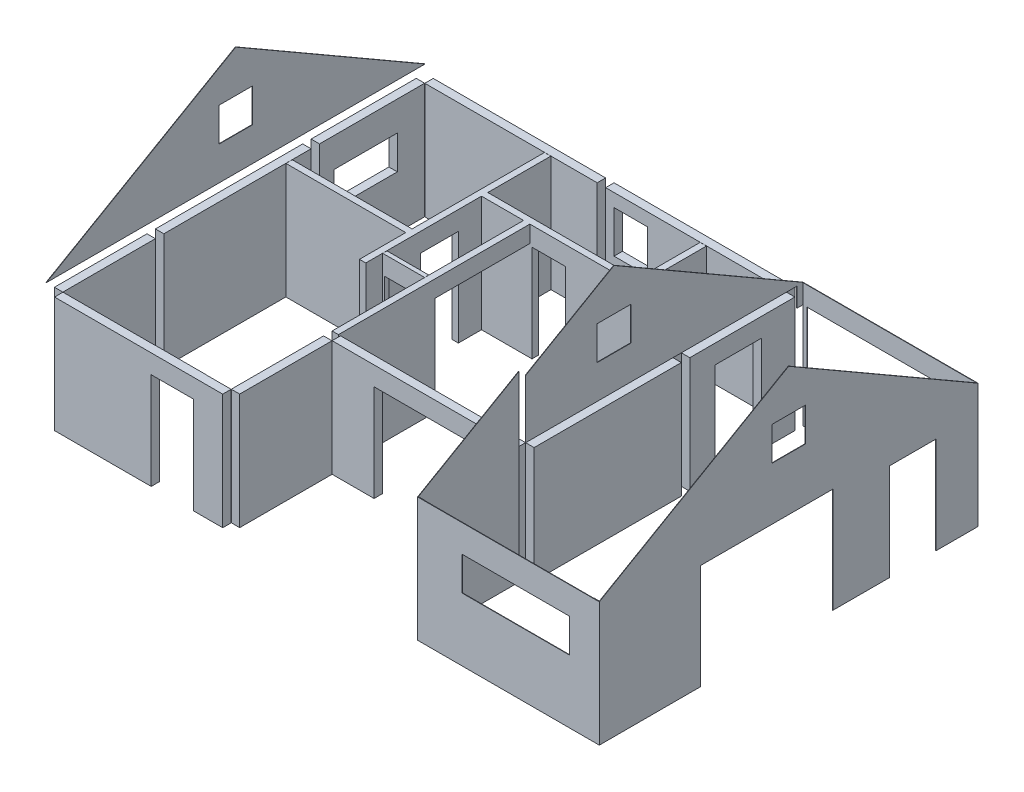
SolidWorks part; units mm, degrees
ref_plane "Спереди" through (0, 0, 0) normal (0, 0, 1) x (1, 0, 0)
ref_plane "Сверху" through (0, 0, 0) normal (0, 1, 0) x (1, 0, 0)
ref_plane "Справа" through (0, 0, 0) normal (1, 0, 0) x (0, 0, -1)
sketch "Эскиз1" plane through (0, 0, 0) normal (0, 1, 0) x (1, 0, 0)
  line L0 (9000, -6600) -> (4400, -6600) construction
  line L1 (0, 0) -> (9000, 0) construction
  line L2 (0, 0) -> (0, -8800) construction
  line L3 (0, -9000) -> (4400, -9000) construction
  line L4 (9000, 0) -> (9000, -6600) construction
  line L5 (4400, -6600) -> (4400, -9000) construction
  line L6 (8800, -203) -> (9000, -203)
  line L7 (203, 0) -> (4300, 0)
  line L8 (203, 0) -> (203, -200)
  line L9 (203, -200) -> (4300, -200)
  line L12 (0, -200) -> (0, -2700)
  line L14 (200, -200) -> (200, -2700)
  line L15 (203, -9000) -> (2500, -9000)
  line L16 (203, -9000) -> (203, -8800)
  line L17 (203, -8800) -> (2500, -8800)
  line L19 (4400, -8797) -> (4200, -8797)
  line L20 (4400, -8797) -> (4400, -6603)
  line L22 (4200, -8797) -> (4200, -6603)
  line L24 (9000, -203) -> (9000, -1000)
  line L26 (8800, -203) -> (8800, -1000)
  line L27 (8797, -6600) -> (7597, -6600)
  line L28 (8797, -6600) -> (8797, -6400)
  line L29 (8797, -6400) -> (7597, -6400)
  line L31 (2500, -8800) -> (2500, -9000)
  line L32 (3500, -8800) -> (3500, -9000)
  line L33 (3500, -8800) -> (4200, -8800)
  line L34 (3500, -9000) -> (4200, -9000)
  line L35 (5597, -6400) -> (5597, -6600)
  line L36 (7597, -6400) -> (7597, -6600)
  line L37 (5597, -6400) -> (4400, -6400)
  line L38 (5597, -6600) -> (4400, -6600)
  line L39 (8800, -1000) -> (9000, -1000)
  line L41 (8800, -2100) -> (9000, -2100)
  line L42 (8800, -2100) -> (8800, -2700)
  line L43 (9000, -2100) -> (9000, -2700)
  line L47 (4200, -6400) -> (4350, -6400)
  line L83 (4200, -6603) -> (4400, -6603)
  line L92 (4200, -4100) -> (4350, -4100)
  line L93 (4200, -4100) -> (4200, -6400)
  line L94 (4350, -4100) -> (4350, -6400)
  line L100 (200, -8800) -> (0, -8800)
  line L101 (4200, -8800) -> (4200, -9000)
  line L102 (4400, -6400) -> (4400, -6600)
  line L103 (8800, -6400) -> (9000, -6400)
  line L104 (0, -200) -> (200, -200)
  line L108 (0, -4500) -> (0, -6400)
  line L109 (200, -4500) -> (200, -6400)
  line L110 (8800, 0) -> (8800, -200)
  line L111 (4300, 0) -> (4300, -200)
  line L113 (4500, 0) -> (4500, -200)
  line L114 (4500, 0) -> (8800, 0)
  line L115 (4500, -200) -> (8800, -200)
  line L116 (0, -9000) -> (0, -8800) construction
  line L117 (-6170.9643, 0) -> (12200, 0) construction
  line L118 (0, 1882.3698) -> (0, -11726.3327) construction
  line L119 (-6170.9643, -4500) -> (10764.3505, -4500) construction
  line L120 (1000, -4500) -> (2250, -4500) construction
  line L121 (-6170.9643, -9000) -> (12200, -9000) construction
  line L122 (1000, -4500) -> (1000, -4600) construction
  line L123 (1000, -4600) -> (2250, -4600) construction
  line L124 (2250, -4500) -> (2250, -4600) construction
  line L125 (1000, -4500) -> (2250, -4600) construction
  line L126 (1000, -4600) -> (2250, -4500) construction
  line L131 (0, -2700) -> (200, -2700)
  line L132 (0, -2900) -> (0, -4500)
  line L137 (3050, -203) -> (3200, -203)
  line L138 (3050, -203) -> (3050, -2400)
  line L139 (3050, -2400) -> (3200, -2400)
  line L140 (3200, -203) -> (3200, -1700)
  line L141 (3050, -203) -> (3200, -2400) construction
  line L142 (3050, -2400) -> (3200, -203) construction
  line L143 (3050, -3300) -> (3200, -3300)
  line L144 (3050, -3300) -> (3050, -3350)
  line L145 (3050, -4600) -> (3200, -4600)
  line L146 (3200, -3300) -> (3200, -4600)
  line L147 (3050, -3300) -> (3200, -4600) construction
  line L148 (3050, -4600) -> (3200, -3300) construction
  line L149 (4150, -4100) -> (4197, -4100)
  line L150 (4150, -4100) -> (4150, -4200)
  line L151 (4150, -4200) -> (4197, -4200)
  line L152 (4197, -4100) -> (4197, -4200)
  line L153 (4150, -4100) -> (4197, -4200) construction
  line L154 (4150, -4200) -> (4197, -4100) construction
  line L155 (203, -3350) -> (3050, -3350)
  line L156 (203, -3350) -> (203, -3500)
  line L157 (203, -3500) -> (3050, -3500)
  line L159 (203, -3350) -> (3050, -3500) construction
  line L160 (203, -3500) -> (3050, -3350) construction
  line L161 (6400, -3500) -> (8800, -3500) construction
  line L162 (4400, 2182.3698) -> (4400, -11426.3327) construction
  line L163 (5200, -1700) -> (6750, -1700)
  line L164 (9000, 2182.3698) -> (9000, -11265.4622) construction
  line L165 (5200, -1700) -> (5200, -1850)
  line L166 (5200, -1850) -> (6900, -1850)
  line L167 (6900, -1700) -> (6900, -1850)
  line L168 (5200, -1700) -> (6900, -1850) construction
  line L169 (5200, -1850) -> (6900, -1700) construction
  line L170 (5800, -2800) -> (8797, -2800) construction
  line L171 (5800, -2800) -> (5800, -2900) construction
  line L172 (5800, -2900) -> (8797, -2900) construction
  line L173 (8797, -2800) -> (8797, -2900) construction
  line L174 (5800, -2800) -> (8797, -2900) construction
  line L175 (5800, -2900) -> (8797, -2800) construction
  line L176 (6750, -203) -> (6900, -203)
  line L177 (6750, -203) -> (6750, -1700)
  line L179 (6900, -203) -> (6900, -1700)
  line L180 (6750, -203) -> (6900, -1700) construction
  line L181 (6750, -1700) -> (6900, -203) construction
  line L186 (3200, -1700) -> (4400, -1700)
  line L188 (3200, -1850) -> (4400, -1850)
  line L189 (4400, -1700) -> (4400, -1850)
  line L190 (3200, -1700) -> (4400, -1850) construction
  line L191 (3200, -1850) -> (4400, -1700) construction
  line L192 (5800, -2900) -> (6400, -2900) construction
  line L193 (5800, -2900) -> (5800, -3500) construction
  line L194 (5800, -3500) -> (6400, -3500) construction
  line L195 (6400, -2900) -> (6400, -3500) construction
  line L196 (5800, -2900) -> (6400, -3500) construction
  line L197 (5800, -3500) -> (6400, -2900) construction
  line L198 (12200, 0) -> (12200, -9000) construction
  line L199 (5350, -4400) -> (5800, -3500) construction
  line L204 (3203, -4100) -> (3250, -4100)
  line L205 (3203, -4100) -> (3203, -4200)
  line L206 (3203, -4200) -> (3250, -4200)
  line L207 (3250, -4100) -> (3250, -4200)
  line L208 (3203, -4100) -> (3250, -4200) construction
  line L209 (3203, -4200) -> (3250, -4100) construction
  line L210 (4350, -4400) -> (5350, -4400) construction
  line L211 (4350, -4400) -> (4350, -6400) construction
  line L212 (4350, -6400) -> (5350, -6400) construction
  line L213 (5350, -4400) -> (5350, -6400) construction
  line L214 (4350, -4400) -> (5350, -6400) construction
  line L215 (4350, -6400) -> (5350, -4400) construction
  line L216 (3200, -1850) -> (3200, -2400)
  line L217 (0, -2900) -> (200, -2900)
  line L218 (200, -2900) -> (200, -4500)
  line L219 (0, -6400) -> (200, -6400)
  line L220 (0, -6600) -> (0, -8800)
  line L221 (0, -6600) -> (200, -6600)
  line L222 (200, -6600) -> (200, -8800)
  line L223 (3050, -3500) -> (3050, -4600)
  line L224 (8800, -2700) -> (9000, -2700)
  line L225 (8800, -2900) -> (8800, -6400)
  line L226 (8800, -2900) -> (9000, -2900)
  line L227 (9000, -2900) -> (9000, -6400)
  point P14 (3226.5, -4150)
  point P17 (7298.5, -2850)
  point P41 (1625, -4550)
  point P52 (3125, -1301.5)
  point P62 (3125, -3950)
  point P67 (4173.5, -4150)
  point P72 (1626.5, -3425)
  point P103 (3800, -1775)
  point P104 (6825, -951.5)
  point P105 (4150, -4150)
  point P108 (6050, -1775)
  point P120 (6750, -951.5)
  point P122 (6100, -3200)
  point P127 (4850, -5400)
  dimension "D2" = 6600
  dimension "D3" = 9000
  dimension "D4" = 200
  dimension "D5" = 3
  dimension "D6" = 3
  dimension "D7" = 3
  dimension "D8" = 9000
  dimension "D9" = 200
  dimension "D10" = 3
  dimension "D11" = 3
  dimension "D12" = 700
  dimension "D13" = 50
  dimension "D14" = 4500
  dimension "D15" = 4000
  dimension "D16" = 100
  dimension "D17" = 800
  dimension "D18" = 4400
  dimension "D19" = 4600
  dimension "D20" = 1000
  dimension "D21" = 800
  dimension "D22" = 2000
  dimension "D23" = 1200
  dimension "D24" = 1100
  dimension "D25" = 3
  dimension "D26" = 200
  dimension "D27" = 1000
  dimension "D29" = 200
  dimension "D30" = 4500
  dimension "D31" = 3
  dimension "D32" = 200
  dimension "D33" = 3
  dimension "D34" = 900
  dimension "D35" = 3
  dimension "D36" = 900
  dimension "D37" = 50
  dimension "D38" = 150
  dimension "D39" = 100
  dimension "D40" = 3
  dimension "D41" = 2850
  dimension "D42" = 3150
  dimension "D43" = 1250
  dimension "D44" = 200
  dimension "D46" = 3550
  dimension "D47" = 1500
  dimension "D48" = 800
  dimension "D49" = 1900
  dimension "D50" = 950
  dimension "D51" = 3
  dimension "D53" = 800
  dimension "D54" = 3
  dimension "D55" = 4450
  dimension "D56" = 3500
  dimension "D57" = 2400
  dimension "D58" = 3000
  dimension "D59" = 1400
  dimension "D60" = 2650
  dimension "D61" = 600
  dimension "D63" = 2900
  dimension "D64" = 2300
  dimension "D65" = 1247
  dimension "D66" = 3200
  dimension "D67" = 2000
  dimension "D68" = 1000
  dimension "D72" = 200
extrude "Бобышка-Вытянуть3" add sketch "Эскиз1" along normal blind 2750 contours L155 | L42 L103 L43 L41 | L26 L39 L24 L6 | L113 L115 L110 L114 | L216 L188 L189 L186 L140 L137 L138 L139 | L179 L176 L177 L163 L165 L166 L167 | L157 L223 L145 L146 L143 L144 L155 L156 | L108 L219 L109 L218 L217 L132 | L222 L221 L220 L100 | L144 L145 L146 L143 | L140 L139 L138 L137 | L27 L36 L29 L28 | L8 L9 L111 L7 | L14 L131 L12 L104 | L100 L108 L132 L217 L218 L109 | L47 L94 L92 L93 | L35 L38 L102 L37 | L171 L172 L173 L170 | L19 L22 L83 L20 | L32 L34 L101 L33 | L15 L31 L17 L16 | L122 L120 L124 L123 | L205 L204 L207 L206 | L150 L149 L152 L151 | L165 L163 L167 L166 | L103 L227 L226 L225 region at (8900, 0, 601.5) region at (8900, 0, 2400) region at (100, 0, 7700) region at (100, 0, 4650) region at (6650, 0, 100) region at (3125, 0, 228.7863) region at (3125, 0, 3332.668) region at (5975, 0, 1723.6698)
sketch "Эскиз2" plane through (0, 0, 0) normal (-1, 0, 0) x (0, 0, 1)
  line L2 (850, 1250) -> (2350, 1250)
  line L3 (850, 1250) -> (850, 2050)
  line L4 (850, 2050) -> (2350, 2050)
  line L5 (2350, 1250) -> (2350, 2050)
  line L7 (200, 0) -> (2700, 0) construction
  line L8 (3350, 2750) -> (3350, 0) construction
  dimension "D1" = 1500
  dimension "D2" = 800
  dimension "D3" = 1250
  dimension "D4" = 1000
extrude "Вырез-Вытянуть2" cut sketch "Эскиз2" against normal blind 250
sketch "Эскиз3" plane through (0, 0, 0) normal (0, 0, -1) x (-1, 0, 0)
  line L0 (-4500, 0) -> (-8800, 0) construction
  line L8 (-5500, 2440) -> (-4700, 2440)
  line L9 (-5500, 2440) -> (-5500, 1440)
  line L10 (-5500, 1440) -> (-4700, 1440)
  line L11 (-4700, 2440) -> (-4700, 1440)
  line L15 (-4500, 2750) -> (-4500, 0) construction
  dimension "D1" = 200
  dimension "D2" = 2440
  dimension "D3" = 800
  dimension "D4" = 1000
  dimension "D5" = 1440
extrude "Вырез-Вытянуть3" cut sketch "Эскиз3" against normal blind 593
sketch "Эскиз4" plane through (0, 2750, 0) normal (0, 1, 0) x (1, 0, 0)
  line L6 (3203, -4100) -> (3250, -4100) construction
  line L7 (3226.5, -4100) -> (4173.5, -4100)
  line L8 (3226.5, -4100) -> (3226.5, -4200)
  line L9 (3226.5, -4200) -> (4173.5, -4200)
  line L10 (4173.5, -4100) -> (4173.5, -4200)
  line L11 (4150, -4200) -> (4197, -4200) construction
  line L13 (3050, -2346.4504) -> (3200, -2346.4504)
  line L14 (3050, -2346.4504) -> (3050, -3325)
  line L15 (3050, -3325) -> (3200, -3325)
  line L16 (3200, -2346.4504) -> (3200, -3325)
  line L19 (4249.5007, -1700) -> (5402.0861, -1700)
  line L20 (4249.5007, -1700) -> (4249.5007, -1850)
  line L21 (4249.5007, -1850) -> (5402.0861, -1850)
  line L22 (5402.0861, -1700) -> (5402.0861, -1850)
  line L24 (5200, -1850) -> (6900, -1850) construction
  line L29 (3050, -203) -> (3050, -2400) construction
  line L30 (5597, -6400) -> (4400, -6400) construction
  line L31 (5423.0031, -6400) -> (7690.4362, -6400)
  line L32 (5423.0031, -6400) -> (5423.0031, -6600)
  line L33 (5423.0031, -6600) -> (7690.4362, -6600)
  line L34 (7690.4362, -6400) -> (7690.4362, -6600)
  line L35 (8797, -6600) -> (7597, -6600) construction
  line L36 (8800, -203) -> (8800, -1000) construction
  line L37 (8800, -900.8258) -> (9000, -900.8258)
  line L38 (8800, -900.8258) -> (8800, -2153.976)
  line L39 (8800, -2153.976) -> (9000, -2153.976)
  line L40 (9000, -900.8258) -> (9000, -2153.976)
  line L41 (9000, -2100) -> (9000, -2700) construction
  line L42 (3500, -9000) -> (4200, -9000) construction
  line L43 (2379.0159, -8797) -> (3597.5552, -8797)
  line L44 (2379.0159, -8797) -> (2379.0159, -9000)
  line L45 (2379.0159, -9000) -> (3597.5552, -9000)
  line L46 (3597.5552, -8797) -> (3597.5552, -9000)
  line L47 (3200, -1850) -> (3200, -2400) construction
  line L48 (3200, -1700) -> (4400, -1700) construction
extrude "Бобышка-Вытянуть4" add sketch "Эскиз4" against normal offset from surface (450 mm away) 2300 up to face at (8900, 0, 601.5)
ref_plane "Плоскость1" through (13000, 0, 0) normal (1, 0, 0) x (0, 0, -1)
sketch "Эскиз5" plane through (13000, 0, 0) normal (1, 0, 0) x (0, 0, -1)
  line L0 (-4500, 5721.2813) -> (-4500, -150) construction
  line L1 (-6600, -150) -> (0, -150) construction
  line L2 (-4500, 5548.0762) -> (-9000, 2950)
  line L3 (-9000, 2950) -> (-9000, 0)
  line L5 (0, 2950) -> (0, 0)
  line L6 (-4500, 5548.0762) -> (0, 2950)
  line L7 (-8800, 0) -> (-9000, 0) construction
  line L8 (-9000, 0) -> (-8750, 0) construction
  line L9 (-9000, 0) -> (0, 0)
extrude "Бобышка-Вытянуть5" add sketch "Эскиз5" along normal blind 150 separate body
sketch "Эскиз6" plane through (13000, 0, 0) normal (1, 0, 0) x (0, 0, -1)
  line L0 (-9000, 0) -> (0, 0) construction
  line L1 (-1000, 2300) -> (-2100, 2300)
  line L2 (-1000, 2300) -> (-1000, 0)
  line L3 (-1000, 0) -> (-2100, 0)
  line L4 (-2100, 2300) -> (-2100, 0)
  line L5 (0, 2494.3376) -> (50, 2494.3376) construction
  line L6 (-6600, -150) -> (-3450, -150)
  line L7 (-6600, -150) -> (-6600, 2494.3376)
  line L8 (-6600, 2494.3376) -> (-3450, 2494.3376)
  line L9 (-3450, -150) -> (-3450, 2494.3376)
  line L10 (-3450, 50) -> (-3450, 2950) construction
  point P11 (-3450, 2494.3376)
  dimension "D1" = 3150
  dimension "D2" = 1100
extrude "Вырез-Вытянуть5" cut sketch "Эскиз6" along normal blind 670
sketch "Эскиз8" plane through (0, 0, 0) normal (-1, 0, 0) x (0, 0, 1)
  line L0 (4500, 5548.0762) -> (0, 2950)
  line L1 (0, 2950) -> (9000, 2950)
  line L2 (9000, 2950) -> (4500, 5548.0762)
  line L3 (4500, 5548.0762) -> (4500, 2950) construction
  line L4 (2350, 1250) -> (2350, 2050) construction
  line L5 (4100, 4550) -> (4900, 4550)
  line L6 (4100, 4550) -> (4100, 3750)
  line L7 (4100, 3750) -> (4900, 3750)
  line L8 (4900, 4550) -> (4900, 3750)
  dimension "D1" = 800
extrude "Бобышка-Вытянуть8" add sketch "Эскиз8" against normal blind 10 separate body
sketch "Эскиз9" plane through (9000, 0, 0) normal (1, 0, 0) x (0, 0, -1)
  line L0 (-6600, 0) -> (-6600, 2950)
  line L1 (-6600, 2750) -> (-6600, 0) construction
  line L2 (-6600, 2950) -> (0, 2950)
  line L3 (0, 2950) -> (-4500, 5548.0762)
  line L4 (-4500, 5548.0762) -> (-9000, 2950)
  line L5 (-9000, 2950) -> (-9000, 0)
  line L6 (-9000, 0) -> (-6600, 0)
extrude "Бобышка-Вытянуть9" add sketch "Эскиз9" against normal blind 170 separate body
sketch "Эскиз10" plane through (0, 0, 0) normal (0, -1, 0) x (1, 0, 0)
  line L0 (13000, 9000) -> (13000, 6600) construction
  line L1 (9000, 9000) -> (13000, 9000)
  line L2 (9000, 9000) -> (9000, 8850)
  line L3 (9000, 8850) -> (13000, 8850)
  line L4 (13000, 9000) -> (13000, 8850)
  line L5 (13150, 9000) -> (13000, 9000) construction
  line L6 (9000, 6600) -> (9000, 0) construction
  line L7 (13000, 0) -> (12250, 0)
  line L8 (13000, 0) -> (13000, 150)
  line L9 (13000, 150) -> (12250, 150)
  line L10 (12250, 0) -> (12250, 150)
  line L11 (9000, 150) -> (9100, 150)
  line L12 (9000, 150) -> (9000, 0)
  line L13 (9000, 0) -> (9100, 0)
  line L14 (9100, 150) -> (9100, 0)
  line L15 (12250, 160) -> (12250, 10) construction
  point P21 (0, 0)
  point P23 (0, 0)
  point P24 (0, 0)
  point P25 (0, 0)
  point P26 (12250, 150)
extrude "Бобышка-Вытянуть10" add sketch "Эскиз10" against normal up to vertex (2950 mm away) up to point (9000, 2950, 9000)
sketch "Эскиз11" plane through (0, 0, 6400) normal (0, 0, -1) x (-1, 0, 0)
  line L0 (-203, 0) -> (-4300, 0) construction
  line L1 (-7597, 2300) -> (-5397, 2300)
  line L2 (-7597, 2300) -> (-7597, -335.5255)
  line L3 (-7597, -335.5255) -> (-5397, -335.5255)
  line L4 (-5397, 2300) -> (-5397, -335.5255)
  line L5 (-12440, 2950) -> (-12440, 50) construction
  line L6 (-2500, 2300) -> (-3500, 2300)
  line L7 (-2500, 2300) -> (-2500, -123.1481)
  line L8 (-2500, -123.1481) -> (-3500, -123.1481)
  line L9 (-3500, 2300) -> (-3500, -123.1481)
  line L11 (-9890, 2300) -> (-12440, 2300)
  line L12 (-9890, 2300) -> (-9890, 1500)
  line L13 (-9890, 1500) -> (-12440, 1500)
  line L14 (-12440, 2300) -> (-12440, 1500)
  line L15 (-9000, 0) -> (-13000, 0) construction
  line L17 (-9890, 2950) -> (-9890, 50) construction
  dimension "D1" = 1500
  dimension "D2" = 800
  dimension "D3" = 2200
  dimension "D4" = 2300
  dimension "D5" = 2550
extrude "Вырез-Вытянуть6" cut sketch "Эскиз11" against normal blind 5123
sketch "Эскиз12" plane through (0, 0, 0) normal (-1, 0, 0) x (0, 0, 1)
  line L0 (2424.8711, 2950) -> (2424.8711, 4350) construction
  line L1 (0, 2950) -> (9000, 2950) construction
  line L2 (4500, 5548.0762) -> (0, 2950) construction
  line L3 (2424.8711, 4350) -> (3290.8965, 4850) construction
  line L4 (3290.8965, 4850) -> (5709.1035, 4850) construction
  line L5 (9000, 2950) -> (4500, 5548.0762) construction
  line L6 (5709.1035, 4850) -> (6575.1289, 4350) construction
  line L7 (6575.1289, 4350) -> (6575.1289, 2950) construction
  line L8 (4500, 5548.0762) -> (4500, 4850) construction
  dimension "D1" = 1900
  dimension "D2" = 2418.2069
  dimension "D3" = 1400
  dimension "D4" = 4150.2577
extrude "Вырез-Вытянуть7" cut sketch "Эскиз8<2>" against normal blind 16606 contours L5 L8 L7 L6
sketch "Эскиз8<2>" plane through (0, 0, 0) normal (-1, 0, 0) x (0, 0, 1) same geometry as "Эскиз8"
sketch "Эскиз13" plane through (0, 0, 0) normal (-1, 0, 0) x (0, 0, 1)
  line L0 (4500, 5548.0762) -> (0, 2950)
  line L1 (0, 2950) -> (0, 0)
  line L2 (0, 0) -> (9000, 0)
  line L3 (9000, 2950) -> (9000, 0) construction
  line L4 (4500, 5548.0762) -> (9000, 2950)
  line L5 (9000, 2950) -> (9000, 0)
  line L7 (4100, 4550) -> (4900, 4550)
  line L8 (4100, 4550) -> (4100, 3750)
  line L9 (4100, 3750) -> (4900, 3750)
  line L10 (4900, 4550) -> (4900, 3750)
  line L11 (850, 2050) -> (2350, 2050)
  line L12 (850, 2050) -> (850, 1250)
  line L13 (850, 1250) -> (2350, 1250)
  line L14 (2350, 2050) -> (2350, 1250)
sketch "Эскиз16" plane through (13150, 0, 0) normal (1, 0, 0) x (0, 0, -1)
  line L0 (-150, 2950) -> (-150, 0) construction
  line L1 (0, 2950) -> (-150, 2950)
  line L2 (0, 2950) -> (0, 2494.3376)
  line L3 (0, 2494.3376) -> (-150, 2494.3376)
  line L4 (-150, 2950) -> (-150, 2494.3376)
  line L5 (-3450, 2494.3376) -> (-6600, 2494.3376) construction
extrude "Бобышка-Вытянуть16" add sketch "Эскиз16" against normal blind 4160
sketch "Эскиз17" plane through (0, 0, 4100) normal (0, 0, -1) x (-1, 0, 0)
  line L0 (-4200, 2750) -> (-4200, 0) construction
  line L1 (-4350, 2750) -> (-4200, 2750)
  line L2 (-4350, 2750) -> (-4350, 2350)
  line L3 (-4350, 2350) -> (-4200, 2350)
  line L4 (-4200, 2750) -> (-4200, 2350)
  dimension "D1" = 400
extrude "Бобышка-Вытянуть17" add sketch "Эскиз17" along normal up to surface (2250 mm away) up to face at (4925, 1262.5, 1850)
sketch "Эскиз18" plane through (0, 2750, 0) normal (0, 1, 0) x (1, 0, 0)
  line L0 (9000, -4500) -> (9000, -9000) construction
  line L1 (8644.5298, 46.0605) -> (8990, 46.0605)
  line L2 (8644.5298, 46.0605) -> (8644.5298, -6600)
  line L3 (8644.5298, -6600) -> (8990, -6600)
  line L4 (8990, 46.0605) -> (8990, -6600)
  line L5 (8797, -6600) -> (4400, -6600) construction
  line L6 (13000, -9000) -> (9000, -9000) construction
  line L7 (9392.4652, -10) -> (13140, -10)
  line L8 (9392.4652, -10) -> (9392.4652, -8990)
  line L9 (9392.4652, -8990) -> (13140, -8990)
  line L10 (13140, -10) -> (13140, -8990)
  line L11 (13150, -4500) -> (13150, -9000) construction
  line L12 (9000, 0) -> (13000, 0) construction
  dimension "D1" = 10
  dimension "D2" = 10
  dimension "D3" = 10
  dimension "D4" = 10
extrude "Вырез-Вытянуть8" cut sketch "Эскиз18" along normal blind 5414
sketch "Эскиз19" plane through (0, 0, 0) normal (0, -1, 0) x (1, 0, 0)
  line L0 (8990, 6600) -> (8830, 6600) construction
  line L1 (8840, 6600) -> (11709.562, 6600)
  line L2 (8840, 6600) -> (8840, 8990)
  line L3 (8840, 8990) -> (13140, 8990)
  line L4 (13140, 6600) -> (13140, 8990)
  line L5 (8797, 6600) -> (4400, 6600) construction
  line L6 (8830, 6600) -> (8830, 9000) construction
  line L7 (8830, 9000) -> (9000, 9000) construction
  line L8 (13140, 8990) -> (13140, 10) construction
  line L9 (9000, 10) -> (13140, 10)
  line L10 (13140, 10) -> (13140, 6600)
  line L11 (13140, 10) -> (9392.4652, 10) construction
  line L12 (9000, 0) -> (9000, 150) construction
  line L13 (9000, 10) -> (9000, 150)
  line L14 (9000, 150) -> (11709.562, 6600)
  dimension "D1" = 10
  dimension "D2" = 10
extrude "Вырез-Вытянуть9" cut sketch "Эскиз19" against normal blind 5663
